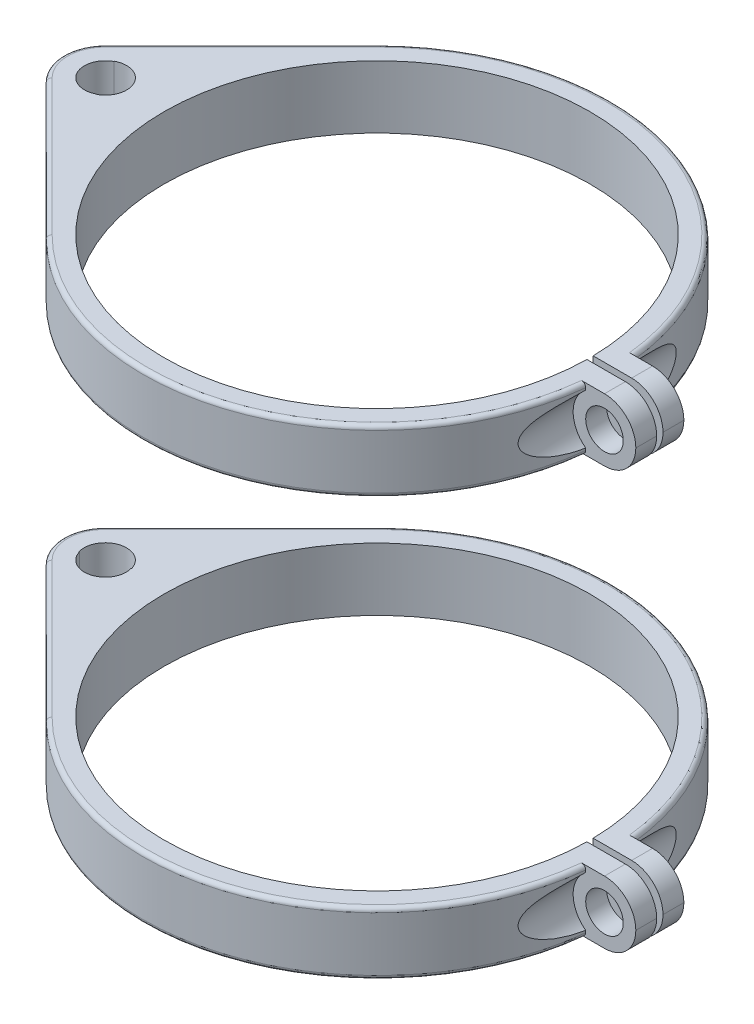
SolidWorks part; units mm, degrees
other "Camera1"
material "1060 Alloy"
ref_plane "Front Plane" through (0, 0, 0) normal (0, 0, 1) x (1, 0, 0)
ref_plane "Top Plane" through (0, 0, 0) normal (0, 1, 0) x (1, 0, 0)
ref_plane "Right Plane" through (0, 0, 0) normal (1, 0, 0) x (0, 0, -1)
sketch "Sketch1" plane through (0, 0, 0) normal (0, 1, 0) x (1, 0, 0)
  line L0 (-39.598, 39.598) -> (-72.1249, 7.0711)
  line L1 (-72.1249, -7.0711) -> (-39.598, -39.598)
  line L2 (50.9945, 0.75) -> (67.704, 0.75)
  line L3 (50.9945, -0.75) -> (67.704, -0.75)
  line L4 (0, 0) -> (67.704, 0) construction
  line L8 (67.704, 0.75) -> (67.704, 5.75)
  line L9 (67.704, 5.75) -> (55.704, 5.75)
  line L11 (67.704, -0.75) -> (67.704, -5.75)
  line L12 (67.704, -5.75) -> (55.704, -5.75)
  line L13 (67.704, 0) -> (67.704, -0.75) construction
  line L14 (67.704, 0.75) -> (67.704, 0) construction
  arc A0 (50.9945, 0.75) -> (50.9945, -0.75) centre (0, 0) ccw
  arc A1 (-39.598, -39.598) -> (55.704, -5.75) centre (0, 0) ccw
  circle A2 centre (-65.0538, 0) radius 5
  arc A3 (-72.1249, 7.0711) -> (-72.1249, -7.0711) centre (-65.0538, 0) ccw
  circle A4 centre (0, 0) radius 56 construction
  circle A5 centre (0, 0) radius 51 construction
  arc A6 (55.704, 5.75) -> (-39.598, 39.598) centre (0, 0) ccw
  point P1 (34.9413, -2.0324)
  point P12 (35.2175, 0.9214)
  dimension "D1" = 102
  dimension "D3" = 10
  dimension "D4" = 5
  dimension "D5" = 45
  dimension "D8" = 5
  dimension "D9" = 12
  dimension "D6" = 1.5
  dimension "D2" = 5
extrude "Boss-Extrude1" add sketch "Sketch1" along normal blind 15
sketch "Sketch3" plane through (0, 0, -5.75) normal (0, 0, -1) x (-1, 0, 0)
  line L0 (-55.704, 7.5) -> (-67.704, 7.5) construction
  line L1 (-55.704, 15) -> (-55.704, 0) construction
  line L2 (-67.704, 15) -> (-67.704, 0) construction
  circle A0 centre (-60.204, 7.5) radius 4.5
  point P8 (-33.2356, 2.5)
  point P9 (-33.2716, 2.5)
  point P10 (-32.6064, 2.5)
  dimension "D1" = 9
extrude "Cut-Extrude2" cut sketch "Sketch3" against normal through all both and the other way through all
sketch "Sketch4" plane through (0, 0, -5.75) normal (0, 0, -1) x (-1, 0, 0)
  circle A0 centre (-60.204, 7.5) radius 7.5
  dimension "D1" = 15
extrude "Cut-Extrude3" cut sketch "Sketch4" along normal blind 15.043
mirror "Mirror8" about plane through (0, 0, 0) normal (0, 0, 1) of "Cut-Extrude3"
fillet "Fillet1" radius 7.5 4 edges at (67.704, 15, -3.25) (67.704, 0, -3.25) (67.704, 0, 3.25) (67.704, 15, 3.25)
fillet "Fillet2" radius 1 10 edges at (18.7423, 0, -52.7705) (-55.8614, 0, -23.3345) (-75.0538, 0, 0) (18.7423, 0, 52.7705) (18.7423, 15, -52.7705) (-55.8614, 15, -23.3345) (-75.0538, 15, 0) (-55.8614, 15, 23.3345) (-55.8614, 0, 23.3345) (18.7423, 15, 52.7705)
ref_plane "Plane2" through (0, 7.5, 0) normal (0, 1, 0) x (1, 0, 0)
sketch3d "3DSketch1"
  line L0 (-65.0538, 7.5, 0) -> (-68.5538, 7.14, -12)
  line L1 (-65.0538, 15, 0) -> (-65.0538, 0, 0) construction
  line L2 (-65.0538, 11.5727, 0) -> (-65.0538, 20.3545, 0) construction
  line L3 (-68.5538, 7.14, -12) -> (-65.0538, 7.5, -12) construction
  line L4 (-65.0538, 7.5, -12) -> (-65.0538, 7.5, 0) construction
  line L5 (-65.0538, 7.5, -12) -> (-68.5538, 7.5, -12) construction
  line L6 (-68.5538, 7.5, -12) -> (-68.5538, 7.14, -12) construction
  circle A0 centre (-65.0538, 15, 0) radius 5 construction
  point P7 (0, 0, 0)
  point P8 (0, 0, 0)
  point P9 (0, 0, 0)
  point P12 (-65.0538, 20, 0)
  point P13 (-45.1259, 2.86, -12)
  point P14 (-37.7259, 1.8913, -12)
  dimension "D1" = 12
  dimension "D3" = 3.5
  dimension "D2" = 0.36
sketch "Sketch5" plane through (0, 0, 0) normal (0, 0, 1) x (1, 0, 0)
  line L1 (-8.443, 57.5) -> (49991.557, 57.5) construction
  circle A1 centre (60.204, 7.5) radius 4.5 construction
  dimension "D1" = 50
ref_plane "Plane1" through (0, 57.5, 0) normal (0, 1, 0) x (1, 0, 0)
mirror "Mirror10" about plane through (0, 57.5, 0) normal (0, 1, 0) of bodies 105
ref_plane "Plane3" through (0, 107.5, 0) normal (0, 1, 0) x (1, 0, 0)
sketch3d "3DSketch3"
  line L0 (-65.0538, 107.5, 0) -> (-65.0538, 107.5, -12) construction
  line L1 (-65.0538, 107.5, -12) -> (-42.5538, 107.5, -12) construction
  line L2 (-42.5538, 107.5, -12) -> (-42.5538, 107.14, -12) construction
  line L3 (-42.5538, 107.14, -12) -> (-65.0538, 107.5, 0)
  circle A0 centre (-65.0538, 115, 0) radius 5 construction
  point P3 (-11.7259, 101.937, -12)
  point P7 (-65.0538, 120, 0)
  dimension "D1" = 12
  dimension "D2" = 22.5
  dimension "D3" = 0.36
sketch "Sketch10" plane through (0, 115, 0) normal (0, 1, 0) x (1, 0, 0)
  line L0 (-67.4538, 4.5) -> (-62.6538, -4.5)
  line L1 (-42.5538, 12) -> (-65.0538, 0) construction
  arc A0 (-62.6538, -4.5) -> (-67.4538, 4.5) centre (-65.0538, 0) ccw
  circle A1 centre (-65.0538, 0) radius 5 construction
  point P7 (0, 0)
  point P8 (0, 0)
  dimension "D1" = 0.1
extrude "Cut-Extrude4" cut sketch "Sketch10" against normal blind 40
sketch "Sketch11" plane through (0, 15, 0) normal (0, 1, 0) x (1, 0, 0)
  line L0 (-60.1578, 1.428) -> (-69.9498, -1.428)
  line L1 (-65.0538, 0) -> (-68.5538, 12) construction
  arc A0 (-60.1578, 1.428) -> (-69.9498, -1.428) centre (-65.0538, 0) ccw
  point P6 (0, 0)
extrude "Cut-Extrude5" cut sketch "Sketch11" against normal blind 40
sketch "Sketch9" plane through (0, 105, 0) normal (0, 1, 0) x (1, 0, 0)
  line L0 (-38.3558, 0) -> (-15.8558, 12)
  dimension "D1" = 28.072
equation "\"MD\" = 102"
equation "\"D1@Sketch1\"=\"MD\""
equation "\"OF\"= 5"
equation "\"D2@Sketch1\"=\"OF\""
equation "\"PD\"= 10"
equation "\"D3@Sketch1\"=\"PD\""
equation "\"D4@Sketch1\"=\"D2@Sketch1\""
equation "\"D8@Sketch1\"=\"D2@Sketch1\""
equation "\"CEX\"= \"TH\" * 0.8"
equation "\"D9@Sketch1\"=\"CEX\""
equation "\"CG\"= 2"
equation "\"FA\" = 45"
equation "\"D5@Sketch1\"=\"FA\""
equation "\"TH\" = 15"
equation "\"D1@Boss-Extrude1\"=\"TH\""
equation "\"D1@Sketch3\"=0.6 * \"TH\""
equation "\"D1@Fillet1\"=\"TH\"/2"
equation "\"H\" = 100"
equation "\"D1@Sketch5\"=\"H\"/2"
equation "\"Mx\" = 1.3'100Nm"
equation "\"Fy\"= 0.72 / 2'100N"
equation "\"Fz\"= 24 / 2'100N"
equation "\"Fx1\" = 19 / 2 - \"Mx\" * 1000 / \"H\"'100N"
equation "\"Fx2\"= 19 / 2 + \"Mx\" * 1000 / \"H\"'100N"
equation "\"D1@3DSketch3\"=\"Fz\""
equation "\"D2@3DSketch3\"=\"Fx2\""
equation "\"D3@3DSketch1\"=abs(\"Fx1\")"
equation "\"D3@3DSketch3\"=\"Fy\""
equation "\"D2@3DSketch1\"=\"Fy\""
equation "\"F1\" = sqr ( \"Fy\" ^ 2 + \"Fz\" ^ 2 + \"Fx1\" ^ 2 ) * 100"
equation "\"F2\"= sqr ( \"Fy\" ^ 2 + \"Fz\" ^ 2 + \"Fx2\" ^ 2 ) * 100"
equation "\"D1@Sketch4\"=\"TH\""
